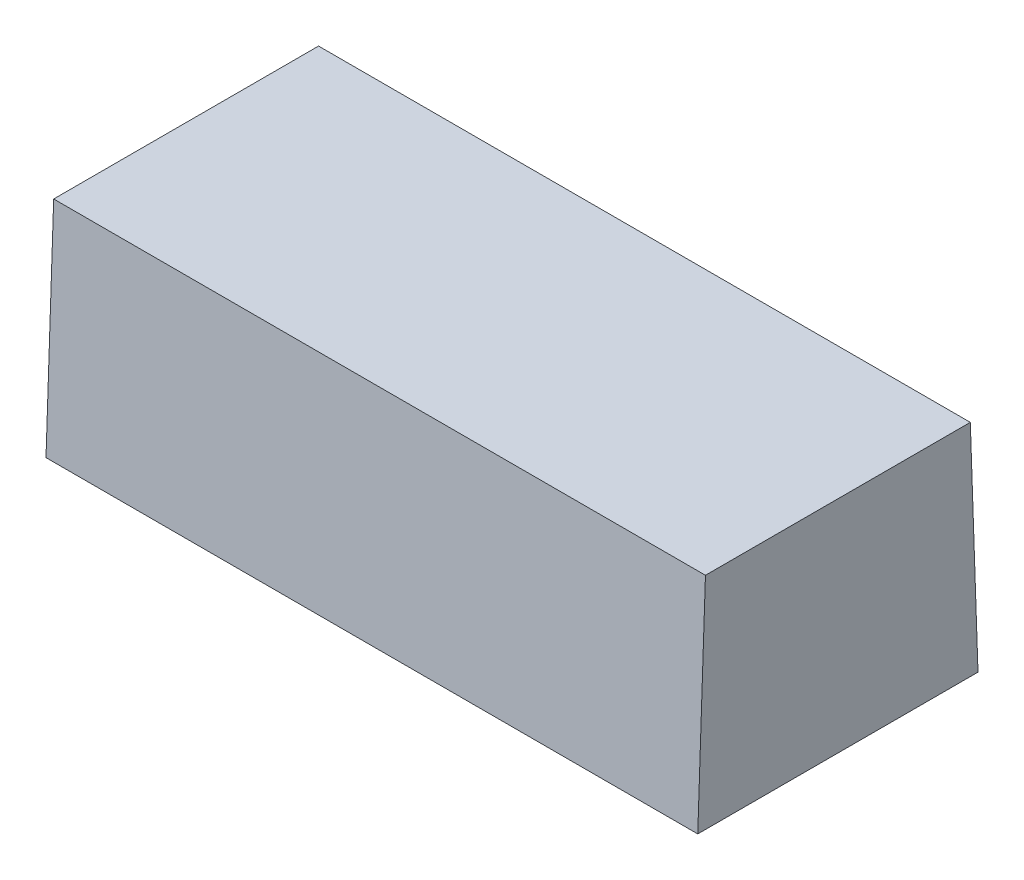
SolidWorks part; units mm, degrees
ref_plane "Front Plane" through (0, 0, 0) normal (0, 0, 1) x (1, 0, 0)
ref_plane "Top Plane" through (0, 0, 0) normal (0, 1, 0) x (1, 0, 0)
ref_plane "Right Plane" through (0, 0, 0) normal (1, 0, 0) x (0, 0, -1)
sketch "Sketch1" plane through (0, 0, 0) normal (1, 0, 0) x (0, 0, -1)
  line L0 (0, 0) -> (0, 38.9723) construction
  line L1 (-17.0647, 0) -> (26.7862, 0) construction
  line L2 (-44.45, -34.925) -> (44.45, -34.925)
  line L3 (44.45, -34.925) -> (42.0108, 34.925)
  line L4 (42.0108, 34.925) -> (-42.0108, 34.925)
  line L5 (-42.0108, 34.925) -> (-44.45, -34.925)
  dimension "D1" = 92
  dimension "D2" = 88.9
  dimension "D3" = 69.85
extrude "Boss-Extrude1" add sketch "Sketch1" along normal blind 206.756
